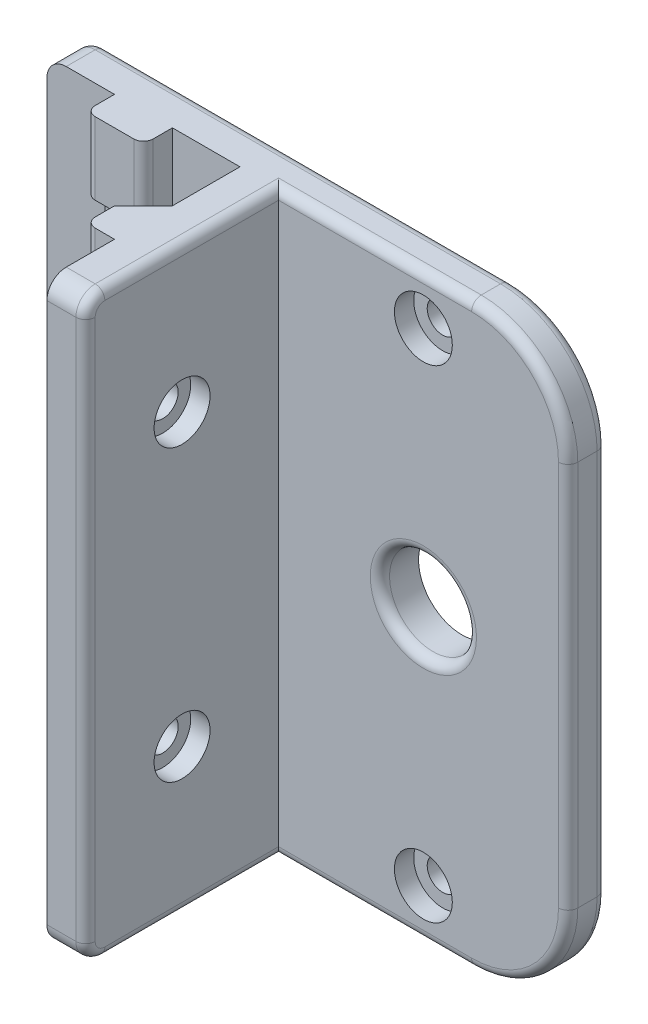
SolidWorks part; units mm, degrees
ref_plane "Front Plane" through (0, 0, 0) normal (0, 0, 1) x (1, 0, 0)
ref_plane "Top Plane" through (0, 0, 0) normal (0, 1, 0) x (1, 0, 0)
ref_plane "Right Plane" through (0, 0, 0) normal (1, 0, 0) x (0, 0, -1)
sketch "Sketch1" plane through (0, 0, 0) normal (0, 1, 0) x (1, 0, 0)
  line L0 (0, 0) -> (-24, 0)
  line L1 (-24, 0) -> (-24, -4)
  line L2 (-24, -4) -> (-4, -4)
  line L3 (-4, -4) -> (-4, -24)
  line L4 (-4, -24) -> (0, -24)
  line L5 (0, -24) -> (0, 0)
  dimension "D1" = 4
  dimension "D2" = 4
  dimension "D3" = 20
  dimension "D4" = 20
extrude "Boss-Extrude1" add sketch "Sketch1" along normal blind 60
sketch "Sketch2" plane through (0, 0, 4) normal (0, 0, 1) x (1, 0, 0)
  line L0 (-14, 60) -> (-14, 0) construction
  line L1 (-24, 60) -> (-4, 60) construction
  line L2 (-24, 0) -> (-4, 0) construction
  line L4 (-11, 0) -> (-17, 0)
  line L5 (-11, 0) -> (-11, 60)
  line L6 (-11, 60) -> (-17, 60)
  line L7 (-17, 0) -> (-17, 60)
  line L8 (-11, 0) -> (-17, 60) construction
  line L9 (-11, 60) -> (-17, 0) construction
  point P6 (-14, 30)
  dimension "D1" = 6
extrude "Boss-Extrude2" add sketch "Sketch2" along normal blind 3
sketch "Sketch3" plane through (-4, 0, 0) normal (-1, 0, 0) x (0, 0, 1)
  line L0 (14, 60) -> (14, 0) construction
  line L1 (4, 60) -> (24, 60) construction
  line L2 (4, 0) -> (24, 0) construction
  line L4 (11, 0) -> (17, 0)
  line L5 (11, 0) -> (11, 60)
  line L6 (11, 60) -> (17, 60)
  line L7 (17, 0) -> (17, 60)
  line L8 (11, 0) -> (17, 60) construction
  line L9 (11, 60) -> (17, 0) construction
  point P6 (14, 30)
  dimension "D1" = 6
extrude "Boss-Extrude3" add sketch "Sketch3" along normal blind 3
sketch "Sketch4" plane through (0, 0, 0) normal (1, 0, 0) x (0, 0, -1)
  line L0 (-12, 0) -> (-12, 60) construction
  line L1 (-24, 0) -> (0, 0) construction
  line L2 (-24, 60) -> (0, 60) construction
  line L3 (0, 60) -> (0, 0) construction
  line L4 (-4, 60) -> (0, 60)
  line L5 (-4, 60) -> (-4, 0)
  line L6 (-4, 0) -> (0, 0)
  line L7 (0, 60) -> (0, 0)
  line L8 (-4, 60) -> (0, 0) construction
  line L9 (-4, 0) -> (0, 60) construction
  point P6 (-2, 30)
  dimension "D1" = 4
extrude "Boss-Extrude4" add sketch "Sketch4" along normal blind 30
sketch "Sketch5" plane through (0, 0, 4) normal (0, 0, -1) x (-1, 0, 0)
  line L0 (-15, 0) -> (-15, 60) construction
  line L3 (0, 30) -> (-30, 30) construction
  line L4 (0, 0) -> (0, 60) construction
  line L5 (-30, 0) -> (-30, 60) construction
  line L6 (-30, 60) -> (0, 60) construction
  line L7 (-30, 0) -> (0, 0) construction
  circle A0 centre (-15, 30) radius 4.5
  circle A1 centre (-15, 5) radius 1.6
  circle A2 centre (-15, 55) radius 1.6
  dimension "D1" = 9
  dimension "D2" = 50
  dimension "D3" = 3.2
extrude "Cut-Extrude1" cut sketch "Sketch5" along normal through all
sketch "Sketch6" plane through (0, 0, 7) normal (0, 0, 1) x (1, 0, 0)
  line L0 (-17, 30) -> (-11, 30) construction
  line L1 (-17, 60) -> (-17, 0) construction
  line L2 (-11, 0) -> (-11, 60) construction
  line L3 (-14, 30) -> (-14, 60) construction
  line L4 (-11, 60) -> (-17, 60) construction
  circle A0 centre (-14, 45) radius 1.6
  circle A1 centre (-14, 15) radius 1.6
  dimension "D1" = 3.2
extrude "Cut-Extrude2" cut sketch "Sketch6" against normal through all
sketch "Sketch7" plane through (0, 0, 7) normal (0, 0, 1) x (1, 0, 0)
  line L0 (-11, 0) -> (-11, 60) construction
  line L1 (-17, 37.5) -> (-11, 37.5)
  line L2 (-17, 37.5) -> (-17, 52.5)
  line L3 (-17, 52.5) -> (-11, 52.5)
  line L4 (-11, 37.5) -> (-11, 52.5)
  line L5 (-17, 37.5) -> (-11, 52.5) construction
  line L6 (-17, 52.5) -> (-11, 37.5) construction
  line L7 (-17, 30) -> (-11, 30) construction
  line L8 (-17, 60) -> (-17, 0) construction
  line L9 (-17, 7.5) -> (-11, 7.5)
  line L10 (-11, 22.5) -> (-11, 7.5)
  line L11 (-17, 22.5) -> (-17, 7.5)
  line L12 (-17, 22.5) -> (-11, 22.5)
  point P0 (-14, 45)
  dimension "D1" = 15
extrude "Cut-Extrude3" cut sketch "Sketch7" against normal blind 2
sketch "Sketch8" plane through (-7, 0, 0) normal (-1, 0, 0) x (0, 0, 1)
  line L0 (11, 30) -> (17, 30) construction
  line L1 (11, 60) -> (11, 0) construction
  line L2 (17, 0) -> (17, 60) construction
  line L3 (14, 60) -> (14, 30) construction
  line L4 (17, 60) -> (11, 60) construction
  circle A0 centre (14, 45) radius 1.6
  circle A1 centre (14, 15) radius 1.6
  dimension "D1" = 3.2
extrude "Cut-Extrude4" cut sketch "Sketch8" against normal through all
chamfer "Chamfer3" distance 3 angle 45 1 edges at (-7, 30, 11)
sketch "Sketch9" plane through (-7, 0, 0) normal (-1, 0, 0) x (0, 0, 1)
  line L0 (11, 30) -> (17, 30) construction
  line L2 (17, 0) -> (17, 60) construction
  line L3 (11, 22.5) -> (11, 7.5)
  line L4 (11, 37.5) -> (17, 37.5)
  line L5 (11, 37.5) -> (11, 52.5)
  line L6 (11, 52.5) -> (17, 52.5)
  line L7 (17, 37.5) -> (17, 52.5)
  line L8 (11, 37.5) -> (17, 52.5) construction
  line L9 (11, 52.5) -> (17, 37.5) construction
  line L10 (11, 22.5) -> (17, 22.5)
  line L11 (17, 22.5) -> (17, 7.5)
  line L12 (11, 7.5) -> (17, 7.5)
  line L13 (11, 60) -> (11, 0) construction
  point P6 (14, 45)
  dimension "D1" = 15
extrude "Cut-Extrude5" cut sketch "Sketch9" against normal blind 2
sketch "Sketch10" plane through (0, 0, 0) normal (1, 0, 0) x (0, 0, -1)
  circle A0 centre (-14, 45) radius 2.9
  circle A1 centre (-14, 15) radius 2.9
  dimension "D1" = 5.8
extrude "Cut-Extrude6" cut sketch "Sketch10" against normal offset from surface (2 mm away) 2 up to face at (-4, 30, 20.5)
sketch "Sketch11" plane through (0, 0, 0) normal (0, 0, -1) x (-1, 0, 0)
  circle A0 centre (14, 45) radius 2.9
  circle A1 centre (14, 15) radius 2.9
  dimension "D1" = 5.8
extrude "Cut-Extrude7" cut sketch "Sketch11" against normal offset from surface (2 mm away) 2 up to face at (-20.5, 30, 4)
sketch "Sketch13" plane through (0, 0, 4) normal (0, 0, 1) x (1, 0, 0)
  circle A0 centre (15, 5) radius 3
  circle A1 centre (15, 55) radius 3
  dimension "D1" = 6
extrude "Cut-Extrude8" cut sketch "Sketch13" against normal blind 2
fillet "Fillet1" radius 2 4 edges at (-24, 0, 2) (-24, 60, 2) (-2, 60, 24) (-2, 0, 24)
fillet "Fillet2" radius 10 2 edges at (30, 0, 2) (30, 60, 2)
fillet "Fillet3" radius 1 28 edges at (27.0711, 2.9289, 0) (-1, 0, 0) (-23.4142, 0.5858, 0) (-24, 30, 0) (-23.4142, 59.4142, 0) (-1, 60, 0) (27.0711, 57.0711, 0) (27.0711, 57.0711, 4) (27.0711, 2.9289, 4) (0, 59.4142, 23.4142) (0, 0.5858, 23.4142) (30, 30, 0) (30, 30, 4) (0, 30, 24) (-7, 56.25, 17) (-7, 30, 17) (-7, 3.75, 17) (-11, 3.75, 7) (-17, 3.75, 7) (-17, 56.25, 7) (-11, 56.25, 7) (-11, 30, 7) (-17, 30, 7) (10.5, 30, 4)
sketch "Sketch12" plane through (0, 0, 2) normal (0, 0, -1) x (-1, 0, 0)
  circle A0 centre (14, 15) radius 1.6 construction
  circle A1 centre (14, 15) radius 1.6
  circle A2 centre (14, 45) radius 1.6 construction
  circle A3 centre (14, 45) radius 1.6
extrude "Boss-Extrude5" add sketch "Sketch12" against normal blind 0.6
